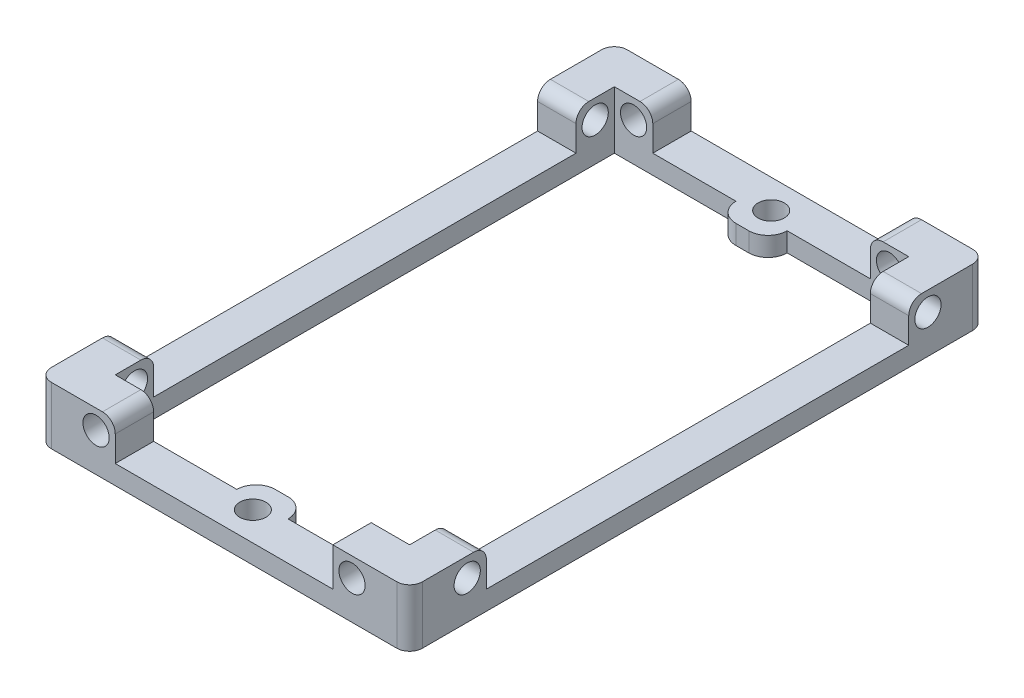
SolidWorks part; units mm, degrees
material "ABS"
ref_plane "Front Plane" through (0, 0, 0) normal (0, 0, 1) x (1, 0, 0)
ref_plane "Top Plane" through (0, 0, 0) normal (0, 1, 0) x (1, 0, 0)
ref_plane "Right Plane" through (0, 0, 0) normal (1, 0, 0) x (0, 0, -1)
sketch "Sketch1" plane through (0, 0, 0) normal (0, 1, 0) x (1, 0, 0)
  line L0 (6, -6) -> (52, -6)
  line L1 (0, 0) -> (58, 0)
  line L2 (0, 0) -> (0, -90)
  line L3 (0, -90) -> (58, -90)
  line L4 (58, 0) -> (58, -90)
  line L5 (52, -6) -> (52, -84)
  line L6 (6, -84) -> (52, -84)
  line L7 (6, -6) -> (6, -84)
  dimension "D1" = 90
  dimension "D2" = 58
  dimension "D3" = 6
extrude "Boss-Extrude1" add sketch "Sketch1" along normal blind 3
sketch "Sketch2" plane through (0, 3, 0) normal (0, 1, 0) x (1, 0, 0)
  line L0 (46, -90) -> (46, -84)
  line L1 (0, -90) -> (58, -90) construction
  line L2 (6, -84) -> (52, -84) construction
  line L3 (52, -78) -> (58, -78)
  line L4 (52, -84) -> (52, -6) construction
  line L5 (58, -90) -> (58, 0) construction
  line L6 (46, -84) -> (52, -84)
  line L7 (46, -90) -> (58, -90)
  line L8 (58, -90) -> (58, -78)
  line L9 (52, -84) -> (52, -78)
  line L10 (0, -45) -> (58, -45) construction
  line L11 (0, 0) -> (0, -90) construction
  line L12 (29, 0) -> (29, -90) construction
  line L13 (58, 0) -> (0, 0) construction
  line L14 (46, 0) -> (46, -6)
  line L15 (46, 0) -> (58, 0)
  line L16 (58, 0) -> (58, -12)
  line L17 (52, -12) -> (58, -12)
  line L18 (52, -6) -> (52, -12)
  line L19 (46, -6) -> (52, -6)
  line L20 (12, -90) -> (12, -84)
  line L21 (12, -90) -> (0, -90)
  line L22 (0, -90) -> (0, -78)
  line L23 (6, -78) -> (0, -78)
  line L24 (6, -84) -> (6, -78)
  line L25 (12, -84) -> (6, -84)
  line L26 (12, -6) -> (6, -6)
  line L27 (12, 0) -> (12, -6)
  line L28 (12, 0) -> (0, 0)
  line L29 (0, 0) -> (0, -12)
  line L30 (6, -12) -> (0, -12)
  line L31 (6, -6) -> (6, -12)
  line M3 (0, 0) -> (0, -90)
  line M4 (0, -90) -> (58, -90)
  line M5 (58, -90) -> (58, 0)
  line M6 (58, 0) -> (0, 0)
  line M7 (52, -84) -> (6, -84)
  line M8 (6, -84) -> (6, -6)
  line M9 (6, -6) -> (52, -6)
  line M10 (52, -6) -> (52, -84)
  dimension "D1" = 6
  dimension "D2" = 6
extrude "Boss-Extrude2" add sketch "Sketch2" along normal blind 6 contours L3 L0 M10 M7 M4 M5 | L17 L14 M10 M5 M6 M9 | L30 L27 M8 M9 M6 M3 | L23 L20 M8 M3 M4 M7 region at (53, 3, 85) region at (5, 3, 85) region at (53, 3, 5) region at (5, 3, 5)
sketch "Sketch3" plane through (0, 0, 0) normal (-1, 0, 0) x (0, 0, 1)
  line L0 (12, 9) -> (6, 9) construction
  line L1 (12, 9) -> (6, 9)
  line L2 (9, 9) -> (9, 3) construction
  line L3 (45, 0) -> (45, 3) construction
  line L8 (0, 0) -> (90, 0)
  line L9 (90, 0) -> (90, 9)
  line L10 (90, 9) -> (78, 9)
  line L11 (78, 9) -> (78, 3)
  line L12 (78, 3) -> (12, 3)
  line L13 (12, 3) -> (12, 9)
  line L14 (12, 9) -> (0, 9)
  line L15 (0, 9) -> (0, 0)
  line L16 (0, 0) -> (90, 0)
  line L17 (90, 0) -> (90, 9)
  line L18 (90, 9) -> (78, 9)
  line L19 (78, 9) -> (78, 3)
  line L20 (78, 3) -> (12, 3)
  line L21 (12, 3) -> (12, 9)
  line L22 (12, 9) -> (0, 9)
  line L23 (0, 9) -> (0, 0)
  circle A0 centre (9, 6) radius 2.05
  circle A1 centre (81, 6) radius 2.05
  dimension "D2" = 4.1
  dimension "D1" = 0
extrude "Cut-Extrude1" cut sketch "Sketch3" against normal through all contours A0 | A1 region at (0, 6, 9) region at (0, 6, 81)
sketch "Sketch4" plane through (0, 0, 0) normal (0, 0, -1) x (-1, 0, 0)
  line L0 (-46, 9) -> (-52, 9) construction
  line L1 (-46, 9) -> (-52, 9)
  line L2 (-46, 9) -> (-46, 3) construction
  line L3 (-46, 9) -> (-46, 3)
  line L4 (-49, 9) -> (-49, 3) construction
  line L5 (-46, 3) -> (-12, 3) construction
  line L6 (-46, 3) -> (-12, 3)
  line L7 (-29, 3) -> (-29, 0) construction
  line L8 (-58, 0) -> (0, 0) construction
  circle A0 centre (-49, 6) radius 2.05
  circle A1 centre (-9, 6) radius 2.05
  dimension "D1" = 4.1
extrude "Cut-Extrude2" cut sketch "Sketch4" against normal through all contours A0 | A1 region at (49, 6, 0) region at (9, 6, 0)
fillet "Fillet1" radius 2 7 edges at (3, 9, 12) (12, 9, 87) (3, 9, 78) (12, 9, 3) (46, 9, 3) (55, 9, 12) (55, 9, 78)
fillet "Fillet2" radius 2 4 edges at (0, 4.5, 90) (58, 4.5, 90) (0, 4.5, 0) (58, 4.5, 0)
sketch "Sketch5" plane through (0, 0, 0) normal (0, -1, 0) x (1, 0, 0)
  line L13 (6, 84) -> (52, 84) construction
  line L14 (33, 84) -> (25, 84)
  line L15 (33, 84) -> (33, 81)
  line L16 (33, 81) -> (25, 81)
  line L17 (25, 84) -> (25, 81)
  line L18 (52, 6) -> (6, 6) construction
  line L19 (33, 6) -> (25, 6)
  line L20 (33, 6) -> (33, 9)
  line L21 (33, 9) -> (25, 9)
  line L22 (25, 6) -> (25, 9)
  line L23 (56, 0) -> (2, 0) construction
  line L24 (56, 0) -> (2, 0)
  point P14 (29, 9)
  point P15 (29, 0)
  point P16 (29, 81)
  line M23 (6, 84) -> (52, 84)
  line M25 (52, 6) -> (6, 6)
  dimension "D1" = 8
  dimension "D2" = 8
  dimension "D3" = 3
  dimension "D4" = 3
extrude "Boss-Extrude3" add sketch "Sketch5" against normal up to surface (3 mm away) contours L22 L20 L21 M25 | L17 L16 L15 M23 region at (29, 0, 82.5) region at (29, 0, 7.5) up to face at (29, 3, 87)
sketch "Sketch6" plane through (0, 0, 0) normal (0, -1, 0) x (1, 0, 0)
  line L0 (33, 9) -> (25, 9) construction
  line L1 (33, 81) -> (25, 81) construction
  line L2 (33, 9) -> (25, 9)
  line L3 (33, 81) -> (25, 81)
  line L4 (29, 81) -> (29, 90) construction
  line L5 (2, 90) -> (56, 90) construction
  line L6 (29, 9) -> (29, 0) construction
  line L7 (56, 0) -> (2, 0) construction
  circle A0 centre (29, 85.5) radius 2.05
  circle A1 centre (29, 4.5) radius 2.05
  dimension "D1" = 4.1
  dimension "D2" = 4.1
extrude "Cut-Extrude3" cut sketch "Sketch6" along direction (0, 1, 0) on the side against the normal up to surface (3 mm away) contours A0 | A1 region at (29, 0, 85.5) region at (29, 0, 4.5) up to face at (29, 3, 84.75)
fillet "Fillet3" radius 3 4 edges at (33, 1.5, 81) (25, 1.5, 81) (33, 1.5, 9) (25, 1.5, 9)
equation "\"Depth\"= 90mm"
equation "\"Height\"= 140mm"
equation "\"Width\"= 64mm"
equation "\"D1@Sketch1\"=\"Depth\""
equation "\"D2@Sketch1\"=\"Width\"-6"
equation "\"4mmPLA\"=4.1"
equation "\"D1@Sketch4\"=\"4mmPLA\""
equation "\"D1@Sketch6\"=\"4mmPLA\""
equation "\"D2@Sketch6\"=\"4mmPLA\""
